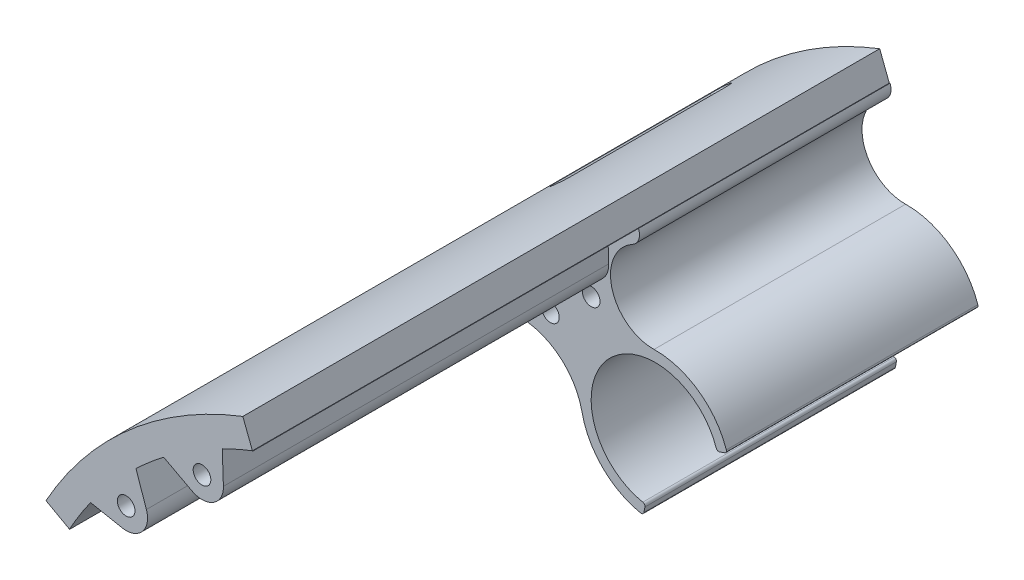
SolidWorks part; units mm, degrees
ref_plane "Front Plane" through (0, 0, 0) normal (1, 0, 0) x (0, 1, 0)
ref_plane "Top Plane" through (0, 0, 0) normal (0, 0, 1) x (0, 1, 0)
ref_plane "Right Plane" through (0, 0, 0) normal (0, 1, 0) x (-1, 0, 0)
sketch "Sketch1" plane through (0, 0, 0) normal (0, 0, 1) x (0, 1, 0)
  line L0 (0, 0) -> (50000, 0) construction
  line L1 (66.793, 25.6394) -> (62.1251, 23.8476)
  line L2 (62.1251, 23.8476) -> (0, 0) construction
  line L3 (34.5874, 62.6291) -> (32.1702, 58.2522)
  line L4 (32.1702, 58.2522) -> (0, 0) construction
  arc A0 (34.5874, 62.6291) -> (66.793, 25.6394) centre (0, 0) cw
  arc A1 (62.1251, 23.8476) -> (32.1702, 58.2522) centre (0, 0) ccw
  dimension "D1" = 71.545
  dimension "D3" = 40.09
  dimension "D4" = 5
  dimension "D2" = 21
extrude "Boss-Extrude1" add sketch "Sketch1" along normal blind 119
ref_axis "Axis1" through (0, 0, 0) along (0, 1, 0)
sketch "Sketch3" plane through (0, 0, 0) normal (0, 0, 1) x (0, 1, 0)
  line L0 (50.1878, 43.6969) -> (30, 20.7) construction
  line L3 (18.2317, 23.0469) -> (16.2704, 23.4381) construction
  line L5 (33.8517, 9.3349) -> (34.4936, 7.4408) construction
  line L6 (33.8517, 9.3349) -> (30, 20.7) construction
  line L7 (30, 20.7) -> (18.2317, 23.0469) construction
  line L8 (16.6629, 22.8499) -> (17.6436, 22.6543)
  line L9 (33.8596, 7.7538) -> (33.5386, 8.7009)
  circle A0 centre (30, 20.7) radius 11.875 construction
  arc A1 (18.2317, 23.0469) -> (33.8517, 9.3349) centre (30, 20.7) cw
  arc A2 (62.1251, 23.8476) -> (32.1702, 58.2522) centre (0, 0) ccw construction
  arc A3 (34.4936, 7.4408) -> (43.9979, 20.944) centre (30, 20.7) ccw
  arc A4 (62.1251, 23.8476) -> (32.1702, 58.2522) centre (0, 0) ccw
  arc A5 (62.1251, 23.8476) -> (58.9977, 24.9546) centre (61.1855, 26.1643) cw
  arc A6 (58.9977, 24.9546) -> (43.9979, 20.944) centre (51.9967, 21.0835) ccw
  arc A7 (32.1702, 58.2522) -> (32.6763, 55.1327) centre (34.3356, 57.0027) ccw
  arc A8 (32.6763, 55.1327) -> (27.1526, 34.4074) centre (24.712, 46.1566) cw
  arc A9 (27.1526, 34.4074) -> (16.2704, 23.4381) centre (30, 20.7) ccw
  arc A10 (16.2704, 23.4381) -> (16.6629, 22.8499) centre (16.7607, 23.3403) ccw
  arc A11 (17.6436, 22.6543) -> (18.2317, 23.0469) centre (17.7414, 23.1447) ccw
  arc A12 (34.4936, 7.4408) -> (33.8596, 7.7538) centre (34.3331, 7.9143) cw
  arc A14 (33.5386, 8.7009) -> (33.8517, 9.3349) centre (34.0121, 8.8614) cw
  point P2 (30, 20.7)
  point P6 (37.9166, 29.7182)
  dimension "D1" = 23.75
  dimension "D2" = 30
  dimension "D4" = 120
  dimension "D5" = 12
  dimension "D6" = 2
  dimension "D7" = 2.5
  dimension "D8" = 2.5
  dimension "D9" = 8
  dimension "D10" = 12
  dimension "D11" = 0.5
  dimension "D12" = 0.5
  dimension "D13" = 0.5
  dimension "D14" = 0.5
  dimension "D3" = 20.7
extrude "Boss-Extrude2" add sketch "Sketch3" along normal blind 47
sketch "Sketch4" plane through (0, 0, 0) normal (0, 0, 1) x (0, 1, 0)
  line L0 (40.3051, 40.3051) -> (0, 0) construction
  line L1 (0, 0) -> (46.6917, 32.6939) construction
  line L2 (0, 0) -> (45.7255, 0) construction
  circle A0 centre (40.3051, 40.3051) radius 1.65
  circle A1 centre (46.6917, 32.6939) radius 1.65
  dimension "D1" = 3.3
  dimension "D2" = 57
  dimension "D3" = 35
  dimension "D4" = 10
extrude "Cut-Extrude1" cut sketch "Sketch4" along normal through all
sketch "Sketch5" plane through (0, 0, 0) normal (0, 0, 1) x (0, 1, 0)
  line L0 (40.3051, 40.3051) -> (0, 0) construction
  line L1 (0, 0) -> (46.6917, 32.6939) construction
  line L3 (0, 0) -> (45.7255, 0) construction
  line L5 (43.4805, 40.3051) -> (41.8928, 43.0551)
  line L6 (41.8928, 43.0551) -> (38.7174, 43.0551)
  line L7 (38.7174, 43.0551) -> (37.1297, 40.3051)
  line L8 (37.1297, 40.3051) -> (38.7174, 37.5551)
  line L9 (38.7174, 37.5551) -> (41.8928, 37.5551)
  line L10 (41.8928, 37.5551) -> (43.4805, 40.3051)
  line L11 (49.8671, 32.6939) -> (48.2794, 35.4439)
  line L12 (48.2794, 35.4439) -> (45.104, 35.4439)
  line L13 (45.104, 35.4439) -> (43.5162, 32.6939)
  line L14 (43.5162, 32.6939) -> (45.104, 29.9439)
  line L15 (45.104, 29.9439) -> (48.2794, 29.9439)
  line L16 (48.2794, 29.9439) -> (49.8671, 32.6939)
  circle A2 centre (40.3051, 40.3051) radius 2.75 construction
  circle A3 centre (46.6917, 32.6939) radius 2.75 construction
  dimension "D1" = 35
  dimension "D3" = 5.5
  dimension "D2" = 57
  dimension "D4" = 10
extrude "Cut-Extrude2" cut sketch "Sketch5" against normal blind 2.6 from offset 44
sketch "Sketch6" plane through (0, 0, 0) normal (0, 0, 1) x (0, 1, 0)
  line L0 (49.9334, 35.2866) -> (52.7447, 40.5739)
  line L1 (53.6048, 29.4112) -> (59.5893, 29.6202)
  line L2 (0, 0) -> (56.4334, 35.2635) construction
  line L3 (0, 0) -> (43.6574, 50.2221) construction
  line L4 (37.4347, 48.3439) -> (38.5773, 54.222)
  line L5 (42.6635, 43.7986) -> (48.3254, 45.7481)
  line L6 (0, 0) -> (45.7255, 0) construction
  circle A0 centre (40.3051, 40.3051) radius 2.75 construction
  circle A1 centre (46.6917, 32.6939) radius 2.75 construction
  arc A2 (49.9334, 35.2866) -> (53.6048, 29.4112) centre (53.4652, 33.4088) ccw
  arc A3 (62.1251, 23.8476) -> (32.1702, 58.2522) centre (0, 0) ccw construction
  arc A4 (52.7447, 40.5739) -> (59.5893, 29.6202) centre (0, 0) cw
  circle A5 centre (53.4652, 33.4088) radius 2.75 construction
  arc A6 (62.1251, 23.8476) -> (32.1702, 58.2522) centre (0, 0) ccw construction
  circle A7 centre (41.3612, 47.5807) radius 2.75 construction
  arc A8 (37.4347, 48.3439) -> (42.6635, 43.7986) centre (41.3612, 47.5807) ccw
  arc A9 (38.5773, 54.222) -> (48.3254, 45.7481) centre (0, 0) cw
  dimension "D1" = 5.5
  dimension "D2" = 8
  dimension "D6" = 5.5
  dimension "D3" = 30
  dimension "D4" = 30
  dimension "D5" = 3.5
  dimension "D7" = 30
  dimension "D8" = 30
  dimension "D9" = 3.5
  dimension "D10" = 32
  dimension "D11" = 49
extrude "Boss-Extrude3" add sketch "Sketch6" along normal blind 119 contours A9 L4 A8 L5 | A4 L0 A2 L1 region at (-33.6173, 53.7989, 0) region at (-47.8776, 41.6194, 0)
sketch "Sketch7" plane through (0, 0, 0) normal (0, 0, 1) x (0, 1, 0)
  circle A0 centre (41.3612, 47.5807) radius 1.65
  circle A1 centre (53.4652, 33.4088) radius 1.65
  dimension "D1" = 3.3
  dimension "D2" = 3.3
extrude "Cut-Extrude3" cut sketch "Sketch7" along normal through all
sketch "Sketch8" plane through (0, 0, 0) normal (0, 0, 1) x (0, 1, 0)
  line L1 (44.5367, 47.5807) -> (42.949, 50.3307)
  line L2 (42.949, 50.3307) -> (39.7735, 50.3307)
  line L3 (39.7735, 50.3307) -> (38.1858, 47.5807)
  line L4 (38.1858, 47.5807) -> (39.7735, 44.8307)
  line L5 (39.7735, 44.8307) -> (42.949, 44.8307)
  line L6 (42.949, 44.8307) -> (44.5367, 47.5807)
  line L7 (56.6406, 33.4088) -> (55.0529, 36.1588)
  line L8 (55.0529, 36.1588) -> (51.8775, 36.1588)
  line L9 (51.8775, 36.1588) -> (50.2898, 33.4088)
  line L10 (50.2898, 33.4088) -> (51.8775, 30.6588)
  line L11 (51.8775, 30.6588) -> (55.0529, 30.6588)
  line L12 (55.0529, 30.6588) -> (56.6406, 33.4088)
  circle A0 centre (41.3612, 47.5807) radius 2.75 construction
  circle A1 centre (53.4652, 33.4088) radius 2.75 construction
  dimension "D1" = 5.5
extrude "Cut-Extrude4" cut sketch "Sketch8" against normal blind 2.6 from offset 116
extrude "Cut-Extrude5" cut sketch "Sketch5<2>" along normal blind 2.6 from offset 3
sketch "Sketch5<2>" plane through (0, 0, 0) normal (0, 0, 1) x (0, 1, 0) same geometry as "Sketch5"
sketch "Sketch9" plane through (0, 0, 0) normal (0, 0, 1) x (0, 1, 0)
  line L0 (62.1251, 23.8476) -> (66.793, 25.6394)
  line L1 (32.1702, 58.2522) -> (34.5874, 62.6291)
extrude "Cut-Extrude-Thin1" cut sketch "Sketch9" along normal through all thin thin type mid plane wall 0.3
sketch "Sketch10" plane through (0, 0, 0) normal (0, 0, 1) x (0, 1, 0)
  line L0 (30, 20.7) -> (53.9588, 46.9801) construction
  line L1 (35.447, 29.6434) -> (54.2827, 50.304)
  line L2 (54.2827, 50.304) -> (57.2386, 47.6091)
  line L3 (57.2386, 47.6091) -> (38.403, 26.9485)
  line L4 (38.403, 26.9485) -> (35.447, 29.6434)
  arc A0 (66.7391, 25.7794) -> (34.7186, 62.5564) centre (0, 0) ccw construction
  point P5 (53.9588, 46.9801)
  point P9 (36.925, 28.2959)
  point P12 (55.7606, 48.9565)
  dimension "D1" = 30
  dimension "D2" = 20.7
  dimension "D3" = 4
extrude "Cut-Extrude6" cut sketch "Sketch10" along normal blind 33 from offset 7
fillet "Fillet1" radius 2 4 edges at (-39.6344, 44.5556, 40) (-36.7685, 47.3555, 40) (-39.6344, 44.5556, 7) (-36.7685, 47.3555, 7)
